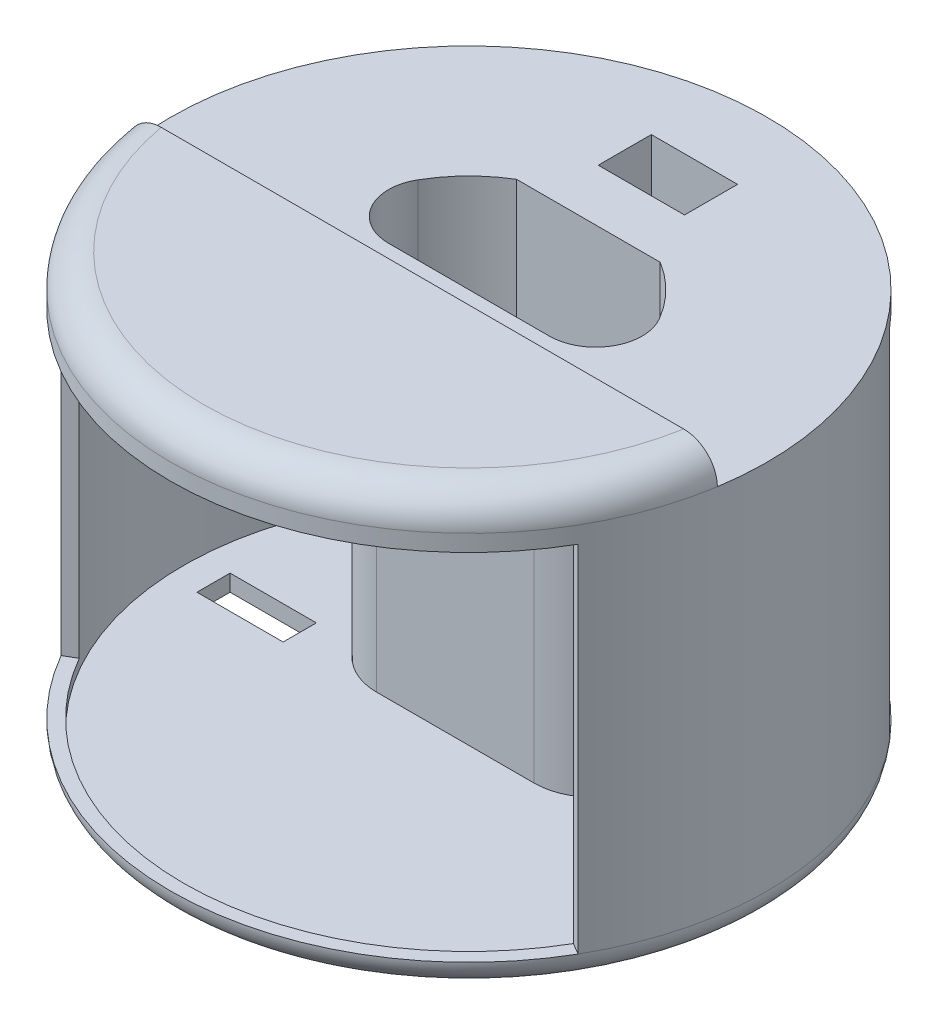
SolidWorks part; units mm, degrees
ref_plane "Front Plane" through (0, 0, 0) normal (0, 0, 1) x (1, 0, 0)
ref_plane "Top Plane" through (0, 0, 0) normal (0, 1, 0) x (1, 0, 0)
ref_plane "Right Plane" through (0, 0, 0) normal (1, 0, 0) x (0, 0, -1)
sketch "Sketch1" plane through (0, 0, 0) normal (0, 0, 1) x (1, 0, 0)
  line L4 (0, 0) -> (0, 76.5) construction
  line L6 (0, 76.5) -> (0, 11.5)
  line L10 (22.5, 0) -> (22.5, 11.5)
  line L11 (22.5, 11.5) -> (0, 11.5)
  line L12 (0, 2) -> (0, 78.1598) construction
  line L13 (25, 11.5) -> (45, 11.5)
  line L15 (22.5, 0) -> (25, 0)
  line L16 (25, 0) -> (25, 11.5)
  line L17 (0, 76.5) -> (40, 76.5)
  line L18 (45, 71.5) -> (45, 11.5)
  arc A3 (45, 71.5) -> (40, 76.5) centre (40, 71.5) ccw
  point P7 (45, 76.5)
  point P8 (45, 11.5)
  point P11 (25, 0)
  point P19 (45, 53.5)
  dimension "D6" = 11.5
  dimension "D7" = 5
  dimension "D1" = 25
  dimension "D2" = 22.5
  dimension "D3" = 11.5
  dimension "D4" = 45
  dimension "D5" = 65
revolve "Revolve1" add sketch "Sketch1" angle 360 about L12
ref_plane "Plane1" through (0, 76.5, 0) normal (0, 1, 0) x (1, 0, 0)
sketch "Sketch5" plane through (0, 76.5, 0) normal (0, 1, 0) x (1, 0, 0)
  line L2 (-45, 0) -> (45, 0)
  arc A1 (45, 0) -> (-45, 0) centre (0, 0) ccw
  dimension "D1" = 45
extrude "Cut-Extrude1" cut sketch "Sketch5" against normal blind 5
ref_plane "Plane3" through (0, 69, 0) normal (0, 1, 0) x (1, 0, 0)
sketch "Sketch7" plane through (0, 11.5, 0) normal (0, -1, 0) x (1, 0, 0)
  line L0 (-21, 0) -> (21, 0)
  line L1 (10.8167, -18) -> (-10.8167, -18)
  arc A0 (-21, 0) -> (21, 0) centre (0, 0) ccw
  circle A2 centre (0, 0) radius 22.5 construction
  dimension "D1" = 21
  dimension "D2" = 1.5
  dimension "D3" = 18
extrude "Cut-Extrude3" cut sketch "Sketch7" against normal blind 60 contours L1 A0 L0
sketch "Sketch8" plane through (0, 69, 0) normal (0, 1, 0) x (1, 0, 0)
  line L0 (-37, 0) -> (37, 0) construction
  line L1 (22.9129, -2) -> (-22.9816, -2)
  line L3 (-10.5739, 20) -> (10.5052, 20)
  circle A0 centre (0, 0) radius 43
  arc A3 (-22.9816, -2) -> (-10.5739, 20) centre (-0.0344, -0.4431) cw
  arc A4 (45, 0) -> (-45, 0) centre (0, 0) ccw construction
  arc A6 (10.5052, 20) -> (22.9129, -2) centre (-0.0344, -0.4431) cw
  dimension "D1" = 2
  dimension "D2" = 22
extrude "Cut-Extrude4" cut sketch "Sketch8" against normal blind 55
ref_plane "Plane4" through (0, 15.5, 0) normal (0, 1, 0) x (1, 0, 0)
ref_plane "Plane5" through (0, 2, 0) normal (0, -1, 0) x (-1, 0, 0)
ref_plane "Plane7" through (0, 5.5, 0) normal (0, -1, 0) x (-1, 0, 0)
fillet "Fillet1" radius 7 2 edges at (21, 41.5, 0) (-21, 41.5, 0)
sketch "Sketch12" plane through (0, 0, 0) normal (1, 0, 0) x (0, 0, -1)
  line L0 (47.3, 15.5) -> (-47.3, 15.5) construction
  line L1 (-48, 69) -> (-41.5, 69)
  line L2 (-48, 69) -> (-48, 15.5)
  line L3 (-48, 15.5) -> (-41.5, 15.5)
  line L4 (-41.5, 69) -> (-41.5, 15.5)
  line L6 (0, 71.5) -> (-45, 71.5) construction
  line L8 (0, 71.5) -> (0, 11.5) construction
  dimension "D1" = 2.5
  dimension "D2" = 6.5
  dimension "D3" = 48
revolve "Cut-Revolve1" cut sketch "Sketch12" angle 60
sketch "Sketch18" plane through (0, 71.5, 0) normal (0, 1, 0) x (1, 0, 0)
  line L0 (-45, 0) -> (-12.1244, 0) construction
  line L1 (-6.5, 34) -> (6.5, 34)
  line L2 (-6.5, 34) -> (-6.5, 26)
  line L3 (-6.5, 26) -> (6.5, 26)
  line L4 (6.5, 34) -> (6.5, 26)
  line L5 (-6.5, 34) -> (6.5, 26) construction
  line L6 (-6.5, 26) -> (6.5, 34) construction
  point P0 (0, 30)
  dimension "D1" = 8
  dimension "D2" = 13
  dimension "D3" = 30
  dimension "D4" = 45
extrude "Cut-Extrude13" cut sketch "Sketch18" against normal blind 5
sketch "Sketch20" plane through (0, 76.5, 0) normal (0, 1, 0) x (1, 0, 0)
  line L1 (50, 0) -> (-50, 0)
  line L2 (50, 0) -> (50, -7)
  line L3 (50, -7) -> (-50, -7)
  line L4 (-50, 0) -> (-50, -7)
  dimension "D1" = 7
  dimension "D2" = 50
  dimension "D3" = 50
extrude "Cut-Extrude15" cut sketch "Sketch20" against normal blind 5
sketch "Sketch19" plane through (0, 0, 7) normal (0, 0, -1) x (-1, 0, 0)
  line L0 (0, 70.6176) -> (0, 16.2649) construction
  line L1 (22, 76.5) -> (-22, 76.5) construction
  circle A0 centre (0, 74) radius 1.5
  circle A1 centre (-30, 74) radius 1.5
  circle A2 centre (29.4522, 74) radius 1.5
  dimension "D1" = 3
  dimension "D7" = 3
  dimension "D8" = 3
  dimension "D2" = 2.5
  dimension "D3" = 15
  dimension "D4" = 15
  dimension "D5" = 2.5
  dimension "D6" = 2.5
extrude "Cut-Extrude14" cut sketch "Sketch19" against normal blind 12
fillet "Fillet3" radius 4 1 edges at (0, 11.5, -45)
ref_plane "Plane8" through (0, 12.5, 0) normal (0, 1, 0) x (1, 0, 0)
sketch "Sketch24" plane through (0, 0, 0) normal (0, -1, 0) x (1, 0, 0)
  line L1 (-1, -21) -> (1, -21)
  line L2 (-1, -21) -> (-1, -24)
  line L3 (-1, -24) -> (1, -24)
  line L4 (1, -21) -> (1, -24)
  line L5 (0, -24) -> (0, -21) construction
  line L6 (-1, -22.5) -> (1, -22.5) construction
  circle A0 centre (0, 0) radius 22.5 construction
  circle A1 centre (0, 0) radius 22.5 construction
  point P0 (0, -22.5)
  dimension "D1" = 3
  dimension "D2" = 2
extrude "Boss-Extrude3" add sketch "Sketch24" against normal blind 2
pattern_circular "CirPattern2" count 5 over 360 about axis through (0, 0, 0) along (0, 1, 0) of "Boss-Extrude3"
sketch "Sketch26" plane through (0, 0, 0) normal (1, 0, 0) x (0, 0, -1)
  line L0 (24.75, 69) -> (-24.75, 69) construction
  line L1 (42.5569, 69) -> (47.5569, 69)
  line L2 (42.5569, 69) -> (42.5569, 15.5)
  line L3 (42.5569, 15.5) -> (47.5569, 15.5)
  line L4 (47.5569, 69) -> (47.5569, 15.5)
  line L5 (47.3, 15.5) -> (-47.3, 15.5) construction
  line L7 (-0.4431, 14) -> (-0.4431, 69) construction
  dimension "D1" = 5
  dimension "D2" = 43
revolve "Cut-Revolve2" cut sketch "Sketch26" angle 50 about axis through (0, 2, 0) along (0, -1, 0)
sketch "Sketch27" plane through (0, 0, 0) normal (0.5, 0, 0.866) x (0.866, 0, -0.5)
sketch "Sketch28" plane through (0, 0, 0) normal (-0.6428, 0, -0.766) x (-0.766, 0, 0.6428)
sketch "Sketch29" plane through (0, 69, 0) normal (0, -1, 0) x (1, 0, 0)
  line L0 (6.5, -26) -> (6.5, -34) construction
  line L1 (8.1, -35.6) -> (-8.1, -35.6)
  line L2 (8.1, -35.6) -> (8.1, -24.4)
  line L3 (8.1, -24.4) -> (-8.1, -24.4)
  line L4 (-8.1, -35.6) -> (-8.1, -24.4)
  line L5 (-6.5, -34) -> (-6.5, -26) construction
  line L6 (6.5, -34) -> (-6.5, -34) construction
  line L7 (-6.5, -26) -> (6.5, -26) construction
  line L8 (6.5, -34) -> (6.5, -26)
  line L9 (6.5, -26) -> (-6.5, -26)
  line L10 (-6.5, -34) -> (-6.5, -26)
  line L11 (6.5, -34) -> (-6.5, -34)
  dimension "D1" = 1.6
  dimension "D2" = 1.6
  dimension "D3" = 1.6
  dimension "D4" = 1.6
  dimension "D5" = 1.6
extrude "Boss-Extrude4" add sketch "Sketch29" along normal blind 19
sketch "Sketch36" plane through (0, 0, -35.6) normal (0, 0, -1) x (-1, 0, 0)
  line L1 (-7.1596, 38.9181) -> (-5.1596, 38.9181)
  line L2 (-7.1596, 38.9181) -> (-7.1596, 36.9181)
  line L3 (-7.1596, 36.9181) -> (-5.1596, 36.9181)
  line L4 (-5.1596, 38.9181) -> (-5.1596, 36.9181)
  line L5 (-6.1596, 36.9181) -> (-6.1596, 38.9181) construction
  line L6 (-7.1596, 37.9181) -> (-5.1596, 37.9181) construction
  point P0 (-6.1596, 37.9181)
  point P4 (-6.1596, 37.9181)
  point P5 (6.0515, 37.9181)
  dimension "D1" = 2
  dimension "D2" = 2
extrude "Boss-Extrude7" add sketch "Sketch36" along normal blind 5
sketch "Sketch37" plane through (5.1596, 0, 0) normal (-1, 0, 0) x (0, 0, 1)
  line L0 (-40.6, 36.9181) -> (-35.6, 36.9181) construction
  line L1 (-40.5974, 38.9181) -> (-38.5974, 38.9181)
  line L2 (-40.5974, 38.9181) -> (-40.5974, 36.9181)
  line L3 (-40.5974, 36.9181) -> (-38.5974, 36.9181)
  line L4 (-38.5974, 38.9181) -> (-38.5974, 36.9181)
  line L5 (-39.5974, 36.9181) -> (-39.5974, 38.9181) construction
  line L6 (-40.5974, 37.9181) -> (-38.5974, 37.9181) construction
  point P0 (-39.5974, 37.9181)
  dimension "D1" = 2
  dimension "D2" = 2
extrude "Boss-Extrude8" add sketch "Sketch37" along normal blind 12.5
sketch "Sketch39" plane through (0, 0, -40.6) normal (0, 0, -1) x (-1, 0, 0)
  line L0 (-5.1596, 38.9181) -> (-7.1596, 38.9181) construction
  line L1 (-7.1596, 38.9181) -> (-7.1596, 36.9181) construction
  point P0 (-6.1596, 37.9181)
  dimension "D1" = 1
  dimension "D2" = 1
sketch "Sketch40" plane through (0, 0, -35.6) normal (0, 0, -1) x (-1, 0, 0)
  line L1 (5.3404, 38.9181) -> (7.3404, 38.9181)
  line L2 (5.3404, 38.9181) -> (5.3404, 36.9181)
  line L3 (5.3404, 36.9181) -> (7.3404, 36.9181)
  line L4 (7.3404, 38.9181) -> (7.3404, 36.9181)
  line L5 (6.3404, 36.9181) -> (6.3404, 38.9181) construction
  line L6 (5.3404, 37.9181) -> (7.3404, 37.9181) construction
  point P0 (6.3404, 37.9181)
  point P1 (-6.1596, 37.9181)
  point P2 (6.3404, 37.9181)
  point P4 (6.3404, 37.9181)
  dimension "D1" = 2
  dimension "D2" = 2
  dimension "D3" = 12.5
extrude "Boss-Extrude9" add sketch "Sketch40" along normal blind 5
ref_plane "Plane10" through (0, 0, -35.6) normal (0, 0, -1) x (-1, 0, 0)
ref_plane "Plane12" through (0, 66, 0) normal (0, -1, 0) x (-1, 0, 0)
sketch "Sketch49" plane through (0, 66, 0) normal (0, -1, 0) x (-1, 0, 0)
  line L1 (4.7002, 32.5398) -> (-5.2998, 32.5398)
  line L2 (4.7002, 32.5398) -> (4.7002, 27.5398)
  line L3 (4.7002, 27.5398) -> (-5.2998, 27.5398)
  line L4 (-5.2998, 32.5398) -> (-5.2998, 27.5398)
  line L5 (-0.2998, 27.5398) -> (-0.2998, 32.5398) construction
  line L6 (4.7002, 30.0398) -> (-5.2998, 30.0398) construction
  point P0 (-0.2998, 30.0398)
  dimension "D1" = 5
  dimension "D2" = 10
fillet "Fillet8" radius 9 2 edges at (22.9129, 41.5, 2) (-22.9816, 41.5, 2)
ref_plane "Plane14" through (0, 14, 0) normal (0, 1, 0) x (1, 0, 0)
sketch "Sketch50" plane through (0, 14, 0) normal (0, 1, 0) x (1, 0, 0)
  line L0 (0, -42.075) -> (0, 42.075) construction
  line L1 (-25.5, -2.5) -> (-38.5, -2.5)
  line L2 (-25.5, -2.5) -> (-25.5, 2.5)
  line L3 (-25.5, 2.5) -> (-38.5, 2.5)
  line L4 (-38.5, -2.5) -> (-38.5, 2.5)
  line L5 (-32, 2.5) -> (-32, -2.5) construction
  line L6 (-25.5, 0) -> (-38.5, 0) construction
  line L7 (25.5, -2.5) -> (38.5, -2.5)
  line L8 (38.5, -2.5) -> (38.5, 2.5)
  line L9 (25.5, -2.5) -> (25.5, 2.5)
  line L10 (25.5, 2.5) -> (38.5, 2.5)
  line L11 (38.5, -2.5) -> (38.5, 2.5)
  line L12 (25.5, 2.5) -> (38.5, 2.5)
  line L13 (25.5, -2.5) -> (25.5, 2.5)
  line L14 (25.5, -2.5) -> (38.5, -2.5)
  point P0 (-32, 0)
  dimension "D1" = 13
  dimension "D2" = 5
  dimension "D3" = 32
extrude "Cut-Extrude23" cut sketch "Sketch50" against normal blind 7 contours L10 L9 L7 L8 | L3 L4 L1 L2
